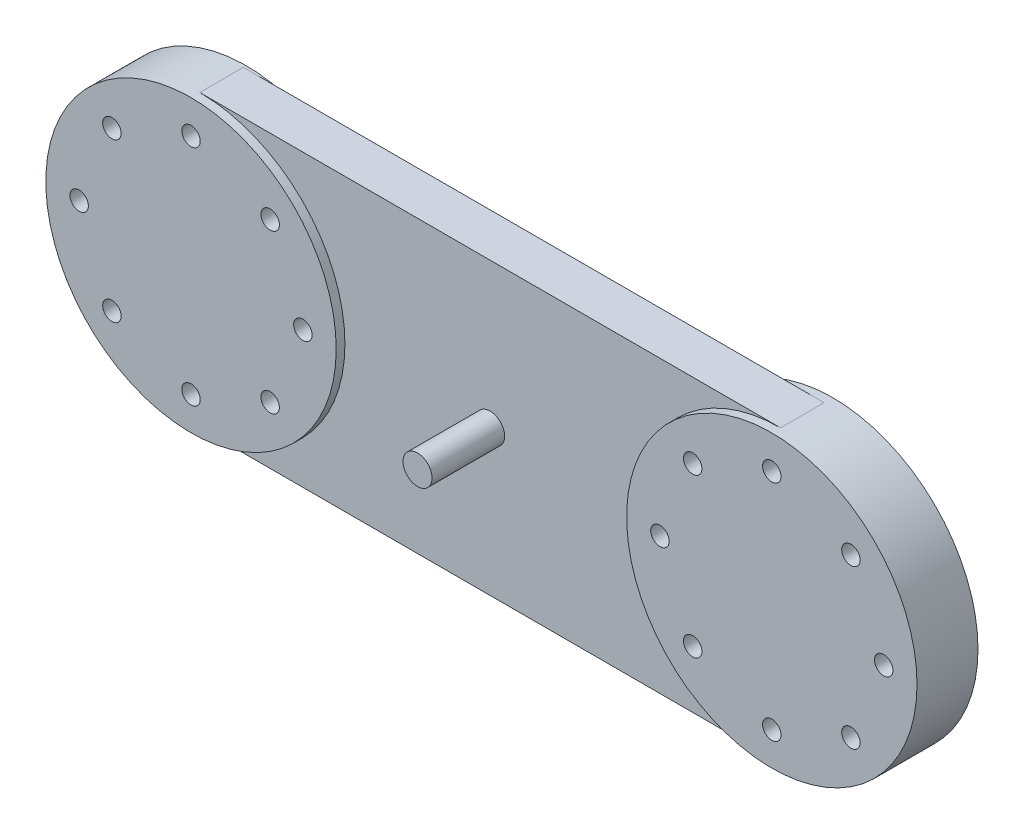
SolidWorks part; units mm, degrees
material "3003 合金"
ref_plane "前视基准面" through (0, 0, 0) normal (0, 0, 1) x (1, 0, 0)
ref_plane "上视基准面" through (0, 0, 0) normal (0, 1, 0) x (1, 0, 0)
ref_plane "右视基准面" through (0, 0, 0) normal (1, 0, 0) x (0, 0, -1)
sketch "草图1" plane through (0, 0, 0) normal (0, 0, 1) x (1, 0, 0)
  line L0 (0, 100) -> (-200, 0) construction
  line L5 (0, 0) -> (-200, 0)
  line L6 (0, 0) -> (0, 100)
  line L7 (0, 100) -> (-200, 100)
  line L8 (-200, 0) -> (-200, 100)
  line L9 (-200, 100) -> (0, 0) construction
  line L10 (-200, 50) -> (-150, 50)
  line L11 (-150, 50) -> (-200, 100) construction
  line L12 (-200, 50) -> (-164.6447, 85.3553) construction
  line L13 (-200, 50) -> (-235.3553, 14.6447)
  line L14 (-100, 50) -> (-100, 0)
  line L15 (-164.6447, 85.3553) -> (-235.3553, 85.3553) construction
  line L16 (-164.6447, 85.3553) -> (-164.6447, 14.6447) construction
  line L17 (-164.6447, 14.6447) -> (-235.3553, 14.6447) construction
  line L18 (-235.3553, 85.3553) -> (-235.3553, 14.6447) construction
  line L19 (-100, 0) -> (-100, 100) construction
  circle A6 centre (0, 50) radius 50
  circle A7 centre (0, 50) radius 25
  circle A8 centre (-200, 50) radius 50
  circle A9 centre (-200, 50) radius 25
  circle A12 centre (-100, 50) radius 5
  circle A13 centre (0, 50) radius 6.5
  circle A14 centre (-161.4697, 50) radius 3.175
  circle A15 centre (-172.7549, 22.7549) radius 3.175
  circle A16 centre (-200, 11.4697) radius 3.175
  circle A17 centre (-227.2451, 22.7549) radius 3.175
  circle A18 centre (-238.5303, 50) radius 3.175
  circle A19 centre (-227.2451, 77.2451) radius 3.175
  circle A20 centre (-200, 88.5303) radius 3.175
  circle A21 centre (-172.7549, 77.2451) radius 3.175
  circle A22 centre (-27.2451, 77.2451) radius 3.175
  circle A23 centre (-38.5303, 50) radius 3.175
  circle A24 centre (-27.2451, 22.7549) radius 3.175
  circle A25 centre (0, 11.4697) radius 3.175
  circle A26 centre (27.2451, 22.7549) radius 3.175
  circle A27 centre (38.5303, 50) radius 3.175
  circle A28 centre (27.2451, 77.2451) radius 3.175
  circle A29 centre (0, 88.5303) radius 3.175
  point P37 (-200, 50)
  dimension "D1" = 100
  dimension "D2" = 200
  dimension "D3" = 50
  dimension "D4" = 50
  dimension "D5" = 10
  dimension "D6" = 13
  dimension "D7" = 6.35
  dimension "D8" = 8
extrude "凸台-拉伸18" add sketch "草图1" along normal blind 13 contours A8 | A6
extrude "凸台-拉伸21" add sketch "草图1<28>" along normal blind 15 contours L5 L8 L7 L6
sketch "草图1<28>" plane through (0, 0, 0) normal (0, 0, 1) x (1, 0, 0) same geometry as "草图1"
extrude "凸台-拉伸22" add sketch "草图1<30>" along normal blind 40 contours A12
sketch "草图1<30>" plane through (0, 0, 0) normal (0, 0, 1) x (1, 0, 0) same geometry as "草图1"
extrude "切除-拉伸2" cut sketch "草图1<31>" along normal blind 41 contours A8
sketch "草图1<31>" plane through (0, 0, 0) normal (0, 0, 1) x (1, 0, 0) same geometry as "草图1"
extrude "凸台-拉伸23" add sketch "草图1<32>" along normal blind 18 and the other way blind 1 contours A8
sketch "草图1<32>" plane through (0, 0, 0) normal (0, 0, 1) x (1, 0, 0) same geometry as "草图1"
extrude "切除-拉伸3" cut sketch "草图1<33>" along normal blind 242.8 contours A13
sketch "草图1<33>" plane through (0, 0, 0) normal (0, 0, 1) x (1, 0, 0) same geometry as "草图1"
extrude "切除-拉伸4" cut sketch "草图1<34>" along normal blind 78 contours A18
sketch "草图1<34>" plane through (0, 0, 0) normal (0, 0, 1) x (1, 0, 0) same geometry as "草图1"
extrude "切除-拉伸5" cut sketch "草图1<35>" against normal blind 69 and the other way blind 130 contours A17 | A16 | A15 | A14 | A21 | A20 | A19
sketch "草图1<35>" plane through (0, 0, 0) normal (0, 0, 1) x (1, 0, 0) same geometry as "草图1"
extrude "切除-拉伸6" cut sketch "草图1<36>" along normal blind 34 contours A6
sketch "草图1<36>" plane through (0, 0, 0) normal (0, 0, 1) x (1, 0, 0) same geometry as "草图1"
extrude "凸台-拉伸24" add sketch "草图1<37>" against normal blind 3 and the other way blind 18 contours A6
sketch "草图1<37>" plane through (0, 0, 0) normal (0, 0, 1) x (1, 0, 0) same geometry as "草图1"
extrude "切除-拉伸7" cut sketch "草图1<39>" along normal blind 136 and the other way blind 164 contours A22 | A23 | A24 | A25 | A26 | A27 | A28 | A29
sketch "草图1<39>" plane through (0, 0, 0) normal (0, 0, 1) x (1, 0, 0) same geometry as "草图1"
extrude "切除-拉伸9" cut sketch "草图1<40>" along normal blind 116 and the other way blind 90 contours A18
sketch "草图1<40>" plane through (0, 0, 0) normal (0, 0, 1) x (1, 0, 0) same geometry as "草图1"
